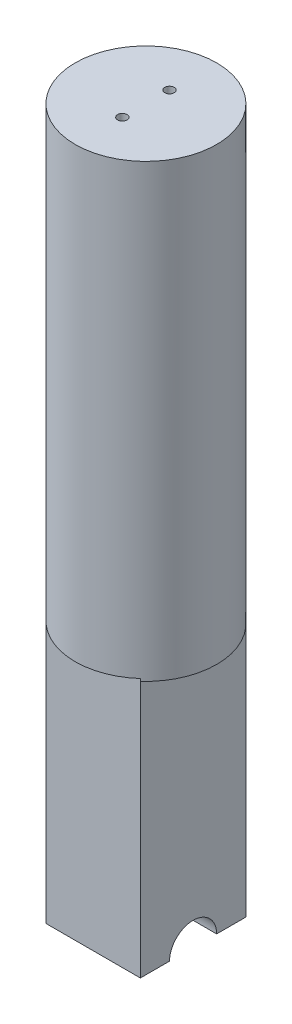
SolidWorks part; units mm, degrees
material "1060 Alloy"
ref_plane "Front Plane" through (0, 0, 0) normal (0, 0, 1) x (1, 0, 0)
ref_plane "Top Plane" through (0, 0, 0) normal (0, 1, 0) x (1, 0, 0)
ref_plane "Right Plane" through (0, 0, 0) normal (1, 0, 0) x (0, 0, -1)
sketch "Sketch2" plane through (0, 0, 0) normal (0, 1, 0) x (1, 0, 0)
  circle A0 centre (0, 0) radius 15
  dimension "D1" = 30
extrude "Boss-Extrude1" add sketch "Sketch2" along normal blind 150
sketch "Sketch3" plane through (0, 0, 0) normal (1, 0, 0) x (0, 0, -1)
  line L0 (15, 0) -> (15, 150) construction
  line L1 (-15, -54.4944) -> (15, -54.4944)
  line L2 (-15, -54.4944) -> (-15, 54.4944)
  line L3 (-15, 54.4944) -> (15, 54.4944)
  line L4 (15, -54.4944) -> (15, 54.4944)
  line L5 (-15, -54.4944) -> (15, 54.4944) construction
  line L6 (-15, 54.4944) -> (15, -54.4944) construction
  point P0 (0, 0)
extrude "Cut-Extrude1" cut sketch "Sketch3" along normal blind 100 from offset 10
extrude "Cut-Extrude2" cut sketch "Sketch3<2>" against normal blind 100 from offset 10 offset against normal yes
sketch "Sketch3<2>" plane through (0, 0, 0) normal (1, 0, 0) x (0, 0, -1) same geometry as "Sketch3"
sketch "Sketch4" plane through (10, 0, 0) normal (1, 0, 0) x (0, 0, -1)
  line L0 (11.1803, 54.4944) -> (11.1803, 0) construction
  line L1 (11.1803, 0) -> (-11.1803, 0) construction
  circle A0 centre (0.0003, 0) radius 5
  dimension "D1" = 10
  dimension "D2" = 11.18
  dimension "D3" = 0
sketch "Sketch5" plane through (0, 0, 0) normal (0, -1, 0) x (1, 0, 0)
  line L1 (-10, 11.1803) -> (10, 11.1803)
  line L3 (-10, -11.1803) -> (10, -11.1803)
  arc A0 (-10, -11.1803) -> (10, -11.1803) centre (0, 0) ccw
  arc A1 (10, 11.1803) -> (-10, 11.1803) centre (0, 0) ccw
  point P0 (0, 0)
extrude "Cut-Extrude4" cut sketch "Sketch5" against normal blind 55
extrude "Cut-Extrude5" cut sketch "Sketch4" against normal through all contours A0
sketch "Sketch6" plane through (0, 150, 0) normal (0, 1, 0) x (1, 0, 0)
  line L0 (0, 5) -> (0, -5) construction
  circle A0 centre (0, 5) radius 1
  circle A1 centre (0, -5) radius 1
  point P4 (0, 0)
  dimension "D2" = 2
  dimension "D3" = 2
  dimension "D1" = 10
extrude "Cut-Extrude6" cut sketch "Sketch6" against normal blind 8
